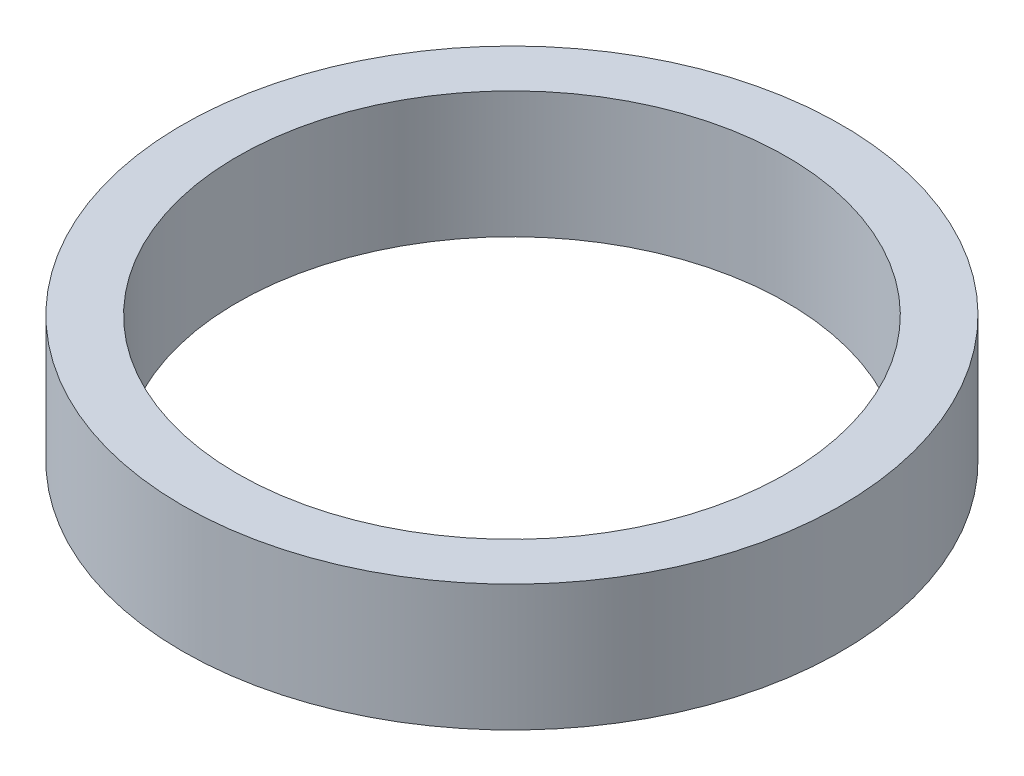
SolidWorks part; units mm, degrees
ref_plane "Front Plane" through (0, 0, 0) normal (0, 0, 1) x (1, 0, 0)
ref_plane "Top Plane" through (0, 0, 0) normal (0, 1, 0) x (1, 0, 0)
ref_plane "Right Plane" through (0, 0, 0) normal (1, 0, 0) x (0, 0, -1)
sketch "Sketch1" plane through (0, 0, 0) normal (0, 1, 0) x (1, 0, 0)
  circle A0 centre (0, 0) radius 60
  dimension "FLANGE_OD" = 120
extrude "Boss-Extrude1" add sketch "Sketch1" along normal blind 23
sketch "Sketch2" plane through (0, 0, 0) normal (0, 1, 0) x (1, 0, 0)
  circle A0 centre (0, 0) radius 50
  dimension "BORE_D" = 100
extrude "Cut-Extrude1" cut sketch "Sketch2" along normal through all
sketch "Sketch3" plane through (0, 23, 0) normal (0, 1, 0) x (1, 0, 0)
  circle A0 centre (0, 0) radius 27.1944 construction
  circle A1 centre (-27.1944, 0) radius 1.6998
  dimension "BOLT_D" = 3.3995
  dimension "BOLT_PCD" = 54.3889
extrude "Cut-Extrude2" cut sketch "Sketch3" against normal blind 13.9797 rebuild error yes
pattern_circular "CirPattern1" count 6 over 360 rebuild error yes
